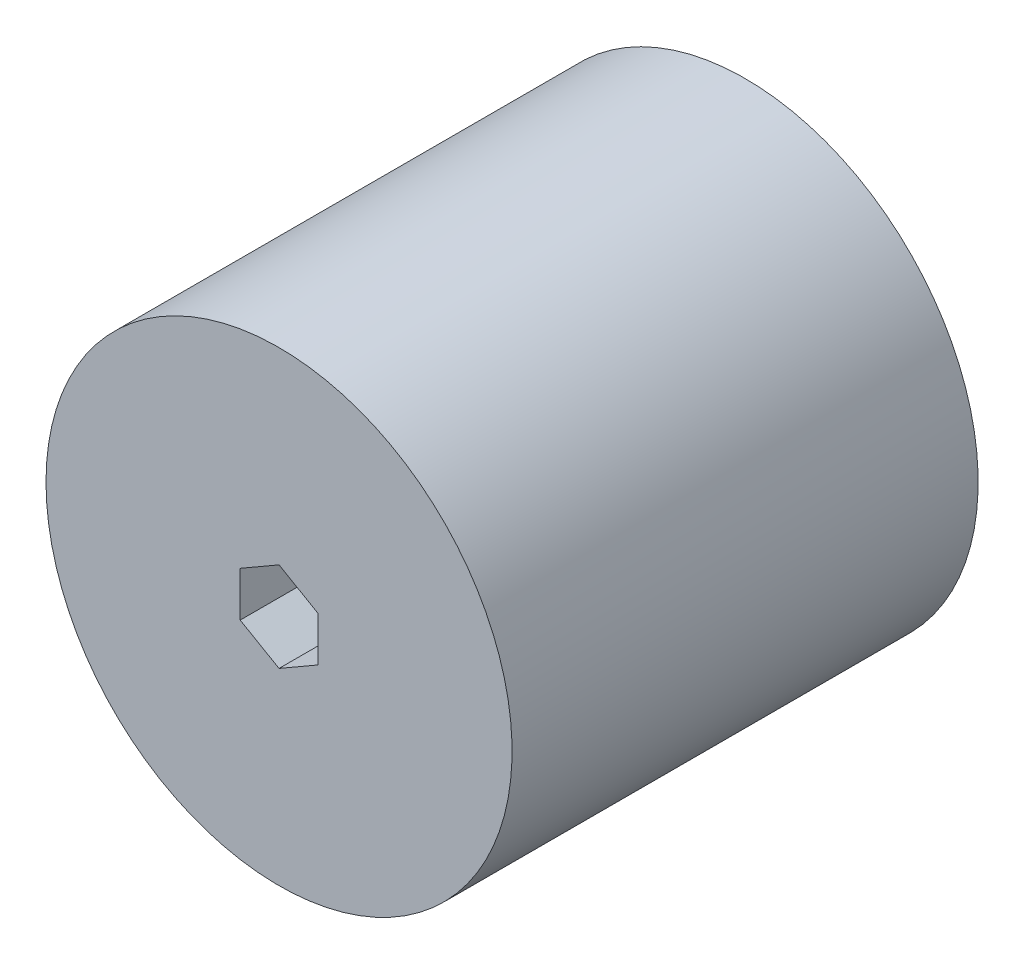
SolidWorks part; units mm, degrees
material "PET"
ref_plane "Front Plane" through (0, 0, 0) normal (0, 0, 1) x (1, 0, 0)
ref_plane "Top Plane" through (0, 0, 0) normal (0, 1, 0) x (1, 0, 0)
ref_plane "Right Plane" through (0, 0, 0) normal (1, 0, 0) x (0, 0, -1)
sketch "Sketch1" plane through (0, 0, 0) normal (0, 0, 1) x (1, 0, 0)
  line L1 (0, 7.3323) -> (-6.35, 3.6662)
  line L2 (-6.35, 3.6662) -> (-6.35, -3.6662)
  line L3 (-6.35, -3.6662) -> (0, -7.3323)
  line L4 (0, -7.3323) -> (6.35, -3.6662)
  line L5 (6.35, -3.6662) -> (6.35, 3.6662)
  line L6 (6.35, 3.6662) -> (0, 7.3323)
  circle A0 centre (0, 0) radius 38.1
  circle A1 centre (0, 0) radius 6.35 construction
  dimension "D1" = 76.2
  dimension "D2" = 12.7
extrude "Boss-Extrude1" add sketch "Sketch1" along normal blind 76.2
